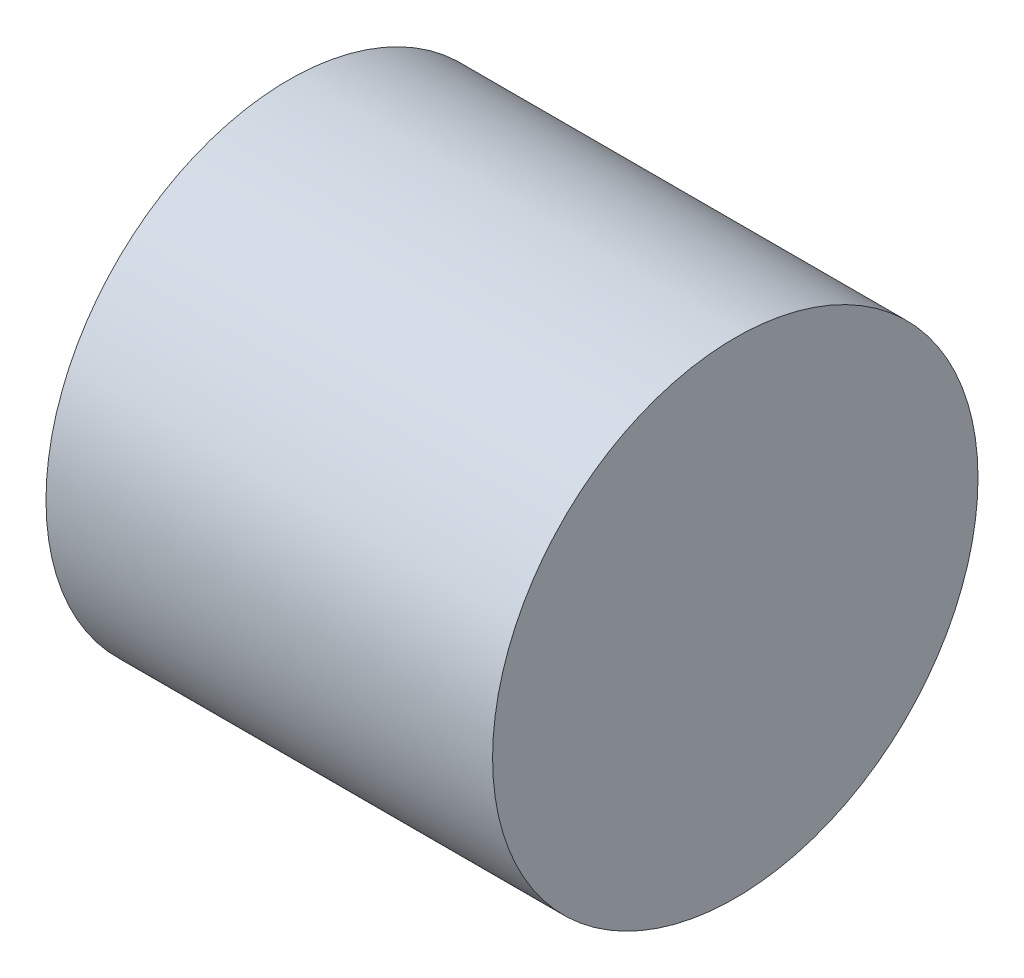
SolidWorks part; units mm, degrees
ref_plane "Front Plane" through (0, 0, 0) normal (0, 0, 1) x (1, 0, 0)
ref_plane "Top Plane" through (0, 0, 0) normal (0, 1, 0) x (1, 0, 0)
ref_plane "Right Plane" through (0, 0, 0) normal (1, 0, 0) x (0, 0, -1)
sketch "Sketch1" plane through (0, 0, 0) normal (1, 0, 0) x (0, 0, -1)
  circle A0 centre (0, 0) radius 12.5
  dimension "D1" = 25
extrude "Boss-Extrude1" add sketch "Sketch1" along normal blind 23
sketch "Sketch2" plane through (0, 0, 0) normal (-1, 0, 0) x (0, 0, 1)
  line L0 (-2.8284, -1) -> (2.8284, -1)
  circle A0 centre (0, 0) radius 3
  dimension "D1" = 6
  dimension "D2" = 1
extrude "Cut-Extrude1" cut sketch "Sketch2" against normal blind 10 contours L0 A0 region at (0, 0.7533, 0)
